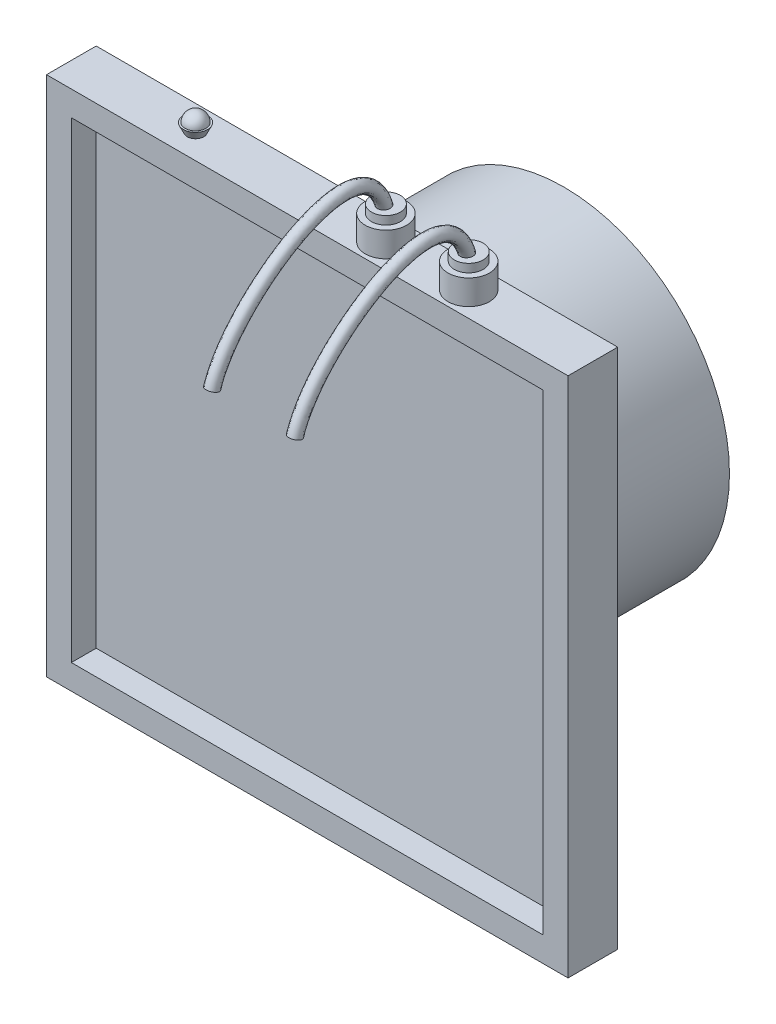
SolidWorks part; units mm, degrees
ref_plane "Ön Düzlem" through (0, 0, 0) normal (0, 0, 1) x (1, 0, 0)
ref_plane "Üst Düzlem" through (0, 0, 0) normal (0, 1, 0) x (1, 0, 0)
ref_plane "Sağ Düzlem" through (0, 0, 0) normal (1, 0, 0) x (0, 0, -1)
sketch "Çizim1" plane through (0, 0, 0) normal (0, 0, 1) x (1, 0, 0)
  line L1 (-28.5, 28.5) -> (28.5, 28.5)
  line L2 (-28.5, 28.5) -> (-28.5, -28.5)
  line L3 (-28.5, -28.5) -> (28.5, -28.5)
  line L4 (28.5, 28.5) -> (28.5, -28.5)
  dimension "D1" = 57
  dimension "D2" = 57
  dimension "D3" = 28.5
  dimension "D4" = 28.5
extrude "Yükseklik-Ekstrüzyon1" add sketch "Çizim1" along normal blind 3
sketch "Çizim2" plane through (0, 0, 0) normal (0, 0, 1) x (1, 0, 0)
  line L5 (-28.5, 28.5) -> (28.5, 28.5)
  line L6 (-28.5, 28.5) -> (-28.5, -28.5)
  line L7 (-28.5, -28.5) -> (28.5, -28.5)
  line L8 (28.5, 28.5) -> (28.5, -28.5)
  line L9 (-31.5, 31.5) -> (31.5, 31.5)
  line L10 (-31.5, 31.5) -> (-31.5, -31.5)
  line L11 (-31.5, -31.5) -> (31.5, -31.5)
  line L12 (31.5, 31.5) -> (31.5, -31.5)
  dimension "D1" = 3
  dimension "D2" = 3
  dimension "D3" = 3
  dimension "D4" = 3
  dimension "D5" = 63
extrude "Yükseklik-Ekstrüzyon2" add sketch "Çizim2" along normal blind 6
sketch "Çizim3" plane through (0, 0, 0) normal (0, 0, -1) x (-1, 0, 0)
  circle A0 centre (0, 0) radius 17.5
  dimension "D1" = 35
extrude "Yükseklik-Ekstrüzyon3" add sketch "Çizim3" along normal blind 10
sketch "Çizim4" plane through (0, 0, -10) normal (0, 0, -1) x (-1, 0, 0)
  circle A0 centre (0, 0) radius 20
  dimension "D1" = 40
extrude "Yükseklik-Ekstrüzyon4" add sketch "Çizim4" along normal blind 15
sketch "Çizim6" plane through (0, 0, -25) normal (0, 0, -1) x (-1, 0, 0)
  circle A0 centre (0, 0) radius 15
  dimension "D1" = 30
extrude "Kes-Ekstrüzyon1" cut sketch "Çizim6" against normal blind 10
chamfer "Pah1" distance 10 angle 45 1 edges at (-15, 0, -15)
sketch "Çizim7" plane through (0, 0, 0) normal (0, 1, 0) x (1, 0, 0)
  line L0 (0, 0) -> (0, 8) construction
  line L1 (-13.0445, 8) -> (15.2402, 8) construction
  line L2 (-15, 8) -> (15, 8)
  arc A0 (15, 8) -> (-15, 8) centre (0, 8) ccw
  dimension "D2" = 30
  dimension "D1" = 8
revolve "Döndür1" add sketch "Çizim7" angle 360 about L2
ref_plane "Düzlem1" through (16.5, 0, 0) normal (1, 0, 0) x (0, 0, -1)
ref_plane "Düzlem2" through (6.5, 0, 0) normal (1, 0, 0) x (0, 0, -1)
sketch "Çizim8" plane through (0, 31.5, 0) normal (0, 1, 0) x (1, 0, 0)
  line L0 (31.5, 0) -> (-31.5, 0) construction
  line L1 (31.5, -6) -> (31.5, 0) construction
  circle A0 centre (16.5, -3) radius 2.5
  circle A1 centre (6.5, -3) radius 2.5
  dimension "D2" = 5
  dimension "D3" = 15
  dimension "D1" = 3
  dimension "D4" = 2
extrude "Yükseklik-Ekstrüzyon5" add sketch "Çizim8" along normal blind 3
sketch "Çizim9" plane through (16.5, 0, 0) normal (1, 0, 0) x (0, 0, -1)
  line L0 (-0.5, 34.5) -> (-5.5, 34.5) construction
  line L1 (0, -31.5) -> (0, 31.5) construction
  spline S0 degree 3 poles (-3, 34.5) (-5.0263, 45.5625) (-21.5134, 34.8913) (-24, 26.663) knots 0 0 0 0 0.763664 0.763664 0.763664 0.763664
  dimension "D1" = 24
sketch "Çizim10" plane through (6.5, 0, 0) normal (1, 0, 0) x (0, 0, -1)
  spline S0 degree 3 poles (-3, 34.5) (-5.0263, 45.5625) (-21.5134, 34.8913) (-24, 26.663) knots 0 0 0 0 0.763664 0.763664 0.763664 0.763664
sweep "Süpür1" add path "Çizim9" circular profile diameter 1.5 parameters "D3"=1.5
sweep "Süpür2" add path "Çizim10" circular profile diameter 1.5 parameters "D3"=1.5
sketch "Çizim45" plane through (0, 34.5, 0) normal (0, 1, 0) x (1, 0, 0)
  circle A0 centre (16.5, -3) radius 1.75
  circle A1 centre (6.5, -3) radius 1.75
  dimension "D1" = 3.5
  dimension "D2" = 2
extrude "Yükseklik-Ekstrüzyon6" add sketch "Çizim45" along normal blind 1
sketch "Çizim46" plane through (0, 31.5, 0) normal (0, 1, 0) x (1, 0, 0)
  line L0 (31.5, 0) -> (-31.5, 0) construction
  line L1 (-31.5, -6) -> (-31.5, 0) construction
  circle A0 centre (-16.5, -3) radius 1
  dimension "D2" = 2
  dimension "D3" = 15
  dimension "D1" = 3
extrude "Yükseklik-Ekstrüzyon7" add sketch "Çizim46" along normal blind 1 draft 25 draft outward yes
sketch "Çizim47" plane through (0, 32.5, 0) normal (0, 1, 0) x (1, 0, 0)
  line L0 (-16.5, -4.4663) -> (-16.5, -1.5337) construction
  line L1 (-16.5, -4.25) -> (-16.5, -1.75)
  circle A0 centre (-16.5, -3) radius 1.4663 construction
  arc A1 (-16.5, -1.75) -> (-16.5, -4.25) centre (-16.5, -3) ccw
  dimension "D1" = 2.5
revolve "Döndür2" add sketch "Çizim47" angle 360 about L0
sketch "Çizim48" plane through (0, 0, 3) normal (0, 0, 1) x (1, 0, 0)
  line L1 (-17.1616, 15.4152) -> (14.4789, 15.4152)
  line L2 (-17.1616, 15.4152) -> (-17.1616, -16.4764)
  line L3 (-17.1616, -16.4764) -> (14.4789, -16.4764)
  line L4 (14.4789, 15.4152) -> (14.4789, -16.4764)
extrude "Kes-Ekstrüzyon2" cut sketch "Çizim48" along normal blind 6
